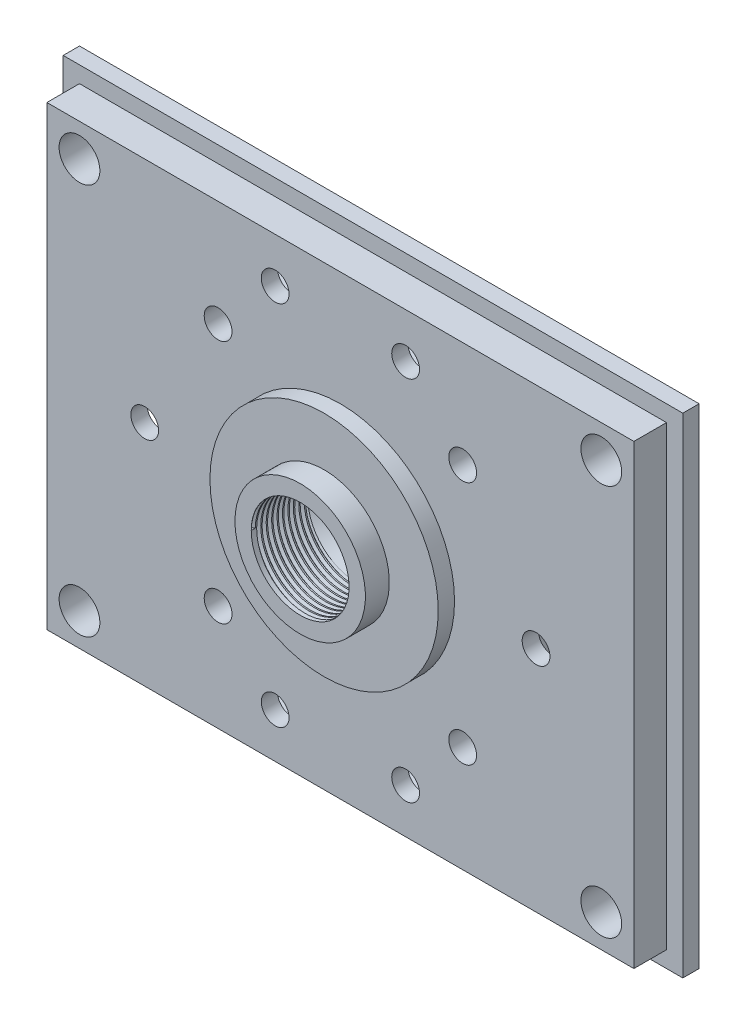
SolidWorks part; units mm, degrees
ref_plane "Front Plane" through (0, 0, 0) normal (0, 0, 1) x (1, 0, 0)
ref_plane "Top Plane" through (0, 0, 0) normal (0, 1, 0) x (1, 0, 0)
ref_plane "Right Plane" through (0, 0, 0) normal (1, 0, 0) x (0, 0, -1)
sketch "Sketch1" plane through (0, 0, 0) normal (0, 0, 1) x (1, 0, 0)
  line L1 (-60.325, 47.625) -> (60.325, 47.625)
  line L2 (-60.325, 47.625) -> (-60.325, -47.625)
  line L3 (-60.325, -47.625) -> (60.325, -47.625)
  line L4 (60.325, 47.625) -> (60.325, -47.625)
  line L5 (-60.325, 47.625) -> (60.325, -47.625) construction
  line L6 (-60.325, -47.625) -> (60.325, 47.625) construction
  point P0 (0, 0)
extrude "Boss-Extrude1" add sketch "Sketch1" along normal blind 3.175
sketch "Sketch3" plane through (0, 0, 0) normal (0, 1, 0) x (1, 0, 0)
  line L0 (0, 0) -> (0, -6.1724) construction
  line L1 (-4.7625, -3.175) -> (-4.7625, 3.175)
  line L3 (-4.7625, 3.175) -> (-22.225, 3.175)
  line L4 (-22.225, 3.175) -> (-22.225, -3.175)
  line L5 (60.325, -3.175) -> (-60.325, -3.175) construction
  line L9 (-12.7, -12.7) -> (-12.7, -17.3595)
  line L10 (-12.7, -17.3595) -> (-9.525, -17.3595)
  line L11 (-9.525, -17.3595) -> (-9.525, -6.35)
  line L12 (-9.525, -6.35) -> (-4.7625, -3.175)
  line L13 (-22.225, -9.525) -> (-22.225, -12.7)
  line L14 (-22.225, -12.7) -> (-12.7, -12.7)
  line L15 (-22.225, -3.175) -> (-22.225, -9.525)
  dimension "D1" = 9.525
  dimension "D2" = 44.45
  dimension "D3" = 19.05
  dimension "D4" = 12.7
  dimension "D6" = 3.175
revolve "Revolve1" add sketch "Sketch3" angle 360 about L0
sketch "Sketch7" plane through (0, 0, 0) normal (0, 0, -1) x (-1, 0, 0)
  circle A1 centre (0, 0) radius 4.7625
  circle A2 centre (0, 0) radius 4.7625
  dimension "D1" = 0
extrude "Cut-Extrude1" cut sketch "Sketch7" against normal through all both and the other way through all
sketch "Sketch21" plane through (0, 0, 0) normal (0, 0, -1) x (-1, 0, 0)
  line L0 (11.2947, 0) -> (-11.2947, 0) construction
  line L1 (0, 11.2947) -> (0, -11.2947) construction
  circle A0 centre (-50.8, -38.1) radius 3.9688
  circle A1 centre (-50.8, 38.1) radius 3.9688
  circle A2 centre (50.8, -38.1) radius 3.9688
  circle A3 centre (50.8, 38.1) radius 3.9688
  dimension "D1" = 50.8
  dimension "D2" = 38.1
extrude "Cut-Extrude2" cut sketch "Sketch21" against normal through all both and the other way through all
sketch "Sketch22" plane through (0, 0, 0) normal (0, 0, -1) x (-1, 0, 0)
  line L0 (-50.8, 32.3453) -> (-50.8, -32.3453)
  line L1 (-50.8, 32.3453) -> (-44.45, 32.3453)
  line L2 (-44.45, 32.3453) -> (-44.45, 38.6953)
  line L3 (-44.45, 38.6953) -> (44.45, 38.6953)
  line L4 (44.45, 38.6953) -> (44.45, 32.3453)
  line L5 (44.45, 32.3453) -> (50.8, 32.3453)
  line L6 (50.8, 32.3453) -> (50.8, -32.3453)
  line L7 (11.2945, 0) -> (-11.2945, 0) construction
  line L8 (44.45, -32.3453) -> (50.8, -32.3453)
  line L9 (44.45, -38.6953) -> (44.45, -32.3453)
  line L10 (-44.45, -38.6953) -> (44.45, -38.6953)
  line L11 (-44.45, -32.3453) -> (-44.45, -38.6953)
  line L12 (-50.8, -32.3453) -> (-44.45, -32.3453)
  point P12 (50.8, 0)
  point P17 (-50.8, 0)
sketch "Sketch23" plane through (0, 0, 3.175) normal (0, 0, 1) x (1, 0, 0)
  line L1 (-57.15, -44.45) -> (57.15, -44.45)
  line L2 (-57.15, -44.45) -> (-57.15, 44.45)
  line L3 (-57.15, 44.45) -> (57.15, 44.45)
  line L4 (57.15, -44.45) -> (57.15, 44.45)
  line L5 (-57.15, -44.45) -> (57.15, 44.45) construction
  line L6 (-57.15, 44.45) -> (57.15, -44.45) construction
  point P0 (0, 0)
extrude "Boss-Extrude2" add sketch "Sketch23" along normal blind 6.35
sketch "Sketch24" plane through (0, 0, 3.175) normal (0, 0, -1) x (-1, 0, 0)
  circle A0 centre (-50.8, -38.1) radius 3.9688 construction
  circle A1 centre (50.8, -38.1) radius 3.9688 construction
  circle A2 centre (50.8, 38.1) radius 3.9688 construction
  circle A3 centre (-50.8, 38.1) radius 3.9688 construction
  circle A4 centre (-50.8, -38.1) radius 3.9688
  circle A5 centre (50.8, -38.1) radius 3.9688
  circle A6 centre (50.8, 38.1) radius 3.9688
  circle A7 centre (-50.8, 38.1) radius 3.9688
extrude "Cut-Extrude3" cut sketch "Sketch24" against normal through all both and the other way through all
extrude "Cut-Extrude4" cut sketch "Sketch22" against normal blind 6.35
sketch "Sketch25" plane through (0, 0, 6.35) normal (0, 0, -1) x (-1, 0, 0)
  line L1 (-31.75, -31.75) -> (31.75, -31.75)
  line L2 (-31.75, -31.75) -> (-31.75, 31.75)
  line L3 (-31.75, 31.75) -> (31.75, 31.75)
  line L4 (31.75, -31.75) -> (31.75, 31.75)
  line L5 (-31.75, -31.75) -> (31.75, 31.75) construction
  line L6 (-31.75, 31.75) -> (31.75, -31.75) construction
  point P0 (0, 0)
extrude "Boss-Extrude3" add sketch "Sketch25" along normal blind 6.35
sketch "Sketch26" plane through (0, 0, 0) normal (0, 0, -1) x (-1, 0, 0)
  circle A1 centre (0, 0) radius 4.7625
  circle A2 centre (0, 0) radius 4.7625
  dimension "D1" = 0
extrude "Cut-Extrude5" cut sketch "Sketch26" against normal through all both and the other way through all
sketch "Sketch27" plane through (0, 0, 0) normal (0, 1, 0) x (1, 0, 0)
  line L0 (-4.7625, -3.175) -> (-9.525, -6.35)
  line L1 (-9.525, -6.35) -> (-9.525, -17.3595)
  line L2 (-9.525, -17.3595) -> (0, -17.3595)
  line L3 (-12.7, -17.3595) -> (12.7, -17.3595) construction
  line L4 (0, -17.3595) -> (0, -3.175)
  line L5 (0, 200000) -> (0, -200006.1724) construction
  line L6 (0, -3.175) -> (-4.7625, -3.175)
revolve "Cut-Revolve1" cut sketch "Sketch27" angle 360 about L0
thread "Thread2" pitch 1.0583 method cut profile "Thread Profile2" start angle 0, offset 0, length 0, pitch 1.0583, diameter 19.05
ref_plane "Plane2" through (-9.525, 0, 17.3595) normal (0, -1, 0) x (-1, 0, 0)
sketch "Thread Profile2" plane through (-9.525, 0, 17.3595) normal (0, -1, 0) x (-1, 0, 0)
  line L0 (0, 0) -> (0, 1.0583) construction
  line L1 (0, 0) -> (0.5728, 0.3307)
  line L2 (0.5728, 0.3307) -> (0.5728, 0.463)
  line L3 (0.5728, 0.463) -> (0, 0.7937)
  line L4 (0.5728, 0.3969) -> (0, 0.3969) construction
  line L11 (0, 0) -> (0, 0.7937)
  point P2 (0, 0)
  dimension "Pitch" = 1.0583
  dimension "Profile_Angle" = 60
  dimension "Profile_Land" = 0.1323
  dimension "Profile_Height" = 0.5728
hole_wizard "1/4-28 Tapped Hole2" positions "Sketch30" profile "Sketch32" tap size "1/4-28" standard "ANSI Inch" end condition up to next
sketch "Sketch30" plane through (0, 0, 0) normal (0, 0, -1) x (-1, 0, 0)
  line L0 (11.2947, 0) -> (-11.2947, 0) construction
  line L1 (0, 11.2947) -> (0, -11.2947) construction
  point P0 (-23.8125, 23.8125)
  point P6 (-23.8125, -23.8125)
  point P9 (23.8125, 23.8125)
  point P10 (23.8125, -23.8125)
  dimension "D1" = 23.8125
  dimension "D2" = 23.8125
sketch "Sketch32" plane through (23.8125, 23.8125, 0) normal (1, 0, 0) x (0, 1, 0)
  line L0 (0, 0) -> (0, 9.525)
  line L1 (0, 9.525) -> (2.7051, 9.525)
  line L2 (2.7051, 9.525) -> (2.7051, 0)
  line L5 (2.7051, 0) -> (0, 0)
  line L11 (0, -6.35) -> (0, 107.95) construction
  dimension "Thru Tap Drill Dia." = 5.4102
  dimension "Thru Tap Drill Depth" = 9.525
cosmetic thread "Hole Thread5" parameters "D2"=6.35
cosmetic thread "Hole Thread6" parameters "D2"=6.35
cosmetic thread "Hole Thread7" parameters "D2"=6.35
cosmetic thread "Hole Thread8" parameters "D2"=6.35
hole_wizard "1/4-28 Tapped Hole3" positions "Sketch33" profile "Sketch34" tap size "1/4-28" standard "ANSI Inch" end condition up to next
sketch "Sketch33" plane through (0, 0, 6.35) normal (0, 0, -1) x (-1, 0, 0)
  line L0 (11.2947, 0) -> (-11.2947, 0) construction
  line L1 (0, 11.2947) -> (0, -11.2947) construction
  point P0 (-12.7, 35.7188)
  point P2 (-38.1, 0)
  point P8 (-12.7, -35.7188)
  point P11 (12.7, 35.7188)
  point P12 (38.1, 0)
  point P13 (12.7, -35.7188)
  dimension "D1" = 12.7
  dimension "D2" = 38.1
  dimension "D3" = 35.7188
sketch "Sketch34" plane through (12.7, 35.7188, 6.35) normal (1, 0, 0) x (0, 1, 0)
  line L0 (0, 0) -> (0, 3.175)
  line L1 (0, 3.175) -> (2.7051, 3.175)
  line L2 (2.7051, 3.175) -> (2.7051, 0)
  line L5 (2.7051, 0) -> (0, 0)
  line L11 (0, -6.35) -> (0, 107.95) construction
  dimension "Thru Tap Drill Dia." = 5.4102
  dimension "Thru Tap Drill Depth" = 3.175
cosmetic thread "Hole Thread9" parameters "D2"=6.35
cosmetic thread "Hole Thread10" parameters "D2"=6.35
cosmetic thread "Hole Thread11" parameters "D2"=6.35
cosmetic thread "Hole Thread12" parameters "D2"=6.35
cosmetic thread "Hole Thread13" parameters "D2"=6.35
cosmetic thread "Hole Thread14" parameters "D2"=6.35
